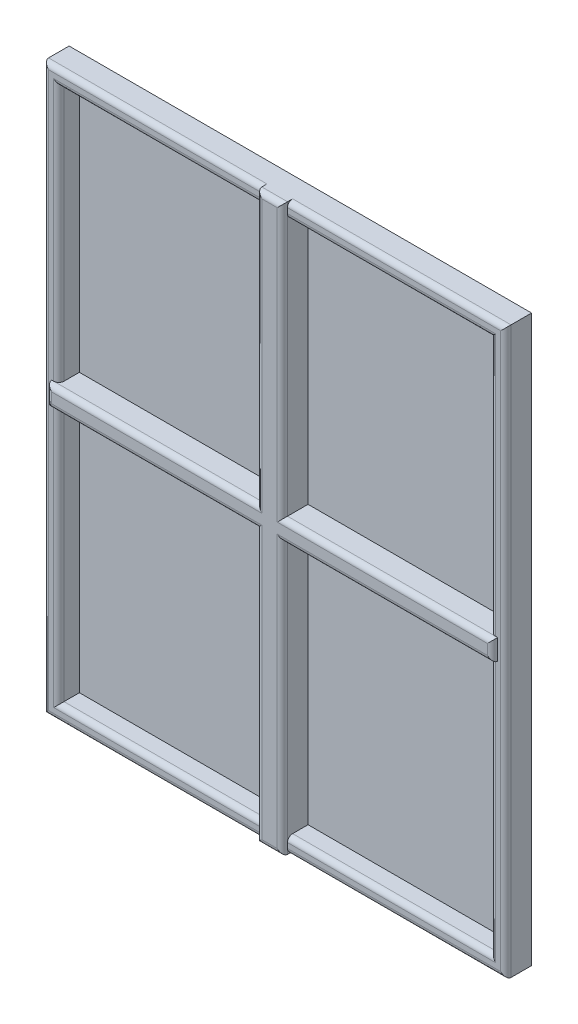
SolidWorks part; units mm, degrees
ref_plane "Front Plane" through (0, 0, 0) normal (0, 0, 1) x (1, 0, 0)
ref_plane "Top Plane" through (0, 0, 0) normal (0, 1, 0) x (1, 0, 0)
ref_plane "Right Plane" through (0, 0, 0) normal (1, 0, 0) x (0, 0, -1)
sketch "Sketch1" plane through (0, 0, 0) normal (0, 0, 1) x (1, 0, 0)
  line L0 (-420, -520) -> (-420, 520)
  line L1 (-450, -550) -> (450, -550)
  line L2 (-450, -550) -> (-450, 550)
  line L3 (-450, 550) -> (450, 550)
  line L4 (450, -550) -> (450, 550)
  line L5 (-450, -550) -> (450, 550) construction
  line L6 (-450, 550) -> (450, -550) construction
  line L7 (-420, 520) -> (420, 520)
  line L8 (420, -520) -> (420, 520)
  line L9 (-420, -520) -> (420, -520)
  point P0 (0, 0)
  dimension "D1" = 1100
  dimension "D2" = 900
  dimension "D3" = 30
extrude "Boss-Extrude1" add sketch "Sketch1" along normal blind 50
fillet "Fillet1" radius 10 8 edges at (420, 0, 50) (0, 520, 50) (-420, 0, 50) (0, -520, 50) (0, -550, 50) (-450, 0, 50) (0, 550, 50) (450, 0, 50)
sketch "Sketch2" plane through (0, 0, 0) normal (0, 0, 1) x (1, 0, 0)
  line L0 (0, 550) -> (0, -550) construction
  line L1 (-450, 550) -> (450, 550) construction
  line L2 (450, -550) -> (-450, -550) construction
  line L3 (-450, 0) -> (450, 0) construction
  line L4 (-450, -550) -> (-450, 550) construction
  line L5 (450, 550) -> (450, -550) construction
  line L6 (-430, -530) -> (-430, 530) construction
  line L7 (-25, 550) -> (25, 550)
  line L8 (-25, 550) -> (-25, -550)
  line L9 (-25, -550) -> (25, -550)
  line L10 (25, 550) -> (25, -550)
  line L11 (-434, 20) -> (434, 20)
  line L12 (-434, 20) -> (-434, -20)
  line L13 (-434, -20) -> (434, -20)
  line L14 (434, 20) -> (434, -20)
  line L15 (430, 530) -> (430, -530) construction
  dimension "D1" = 4
  dimension "D2" = 4
  dimension "D3" = 40
  dimension "D4" = 50
extrude "Boss-Extrude2" add sketch "Sketch2" along normal blind 60 contours L13 L8 L9 L10 | L12 L11 L14 L13 | L10 L9 L8 L7 region at (0, -285, 0)
fillet "Fillet2" radius 10 12 edges at (0, -550, 60) (-25, -285, 60) (-229.5, -20, 60) (-434, 0, 60) (-229.5, 20, 60) (-25, 285, 60) (0, 550, 60) (25, 285, 60) (229.5, 20, 60) (434, 0, 60) (229.5, -20, 60) (25, -285, 60)
sketch "Sketch3" plane through (0, 0, 0) normal (0, 0, 1) x (1, 0, 0)
  line L1 (-430, 530) -> (430, 530)
  line L2 (-430, 530) -> (-430, -530)
  line L3 (-430, -530) -> (430, -530)
  line L4 (430, 530) -> (430, -530)
extrude "Boss-Extrude3" add sketch "Sketch3" along normal blind 10 separate body
scale "Scale2" bodies to scale 102 103 scale about origin uniform scaling yes scale factor 0.25
scale "Scale3" bodies to scale 105 106 scale about origin uniform scaling yes scale factor 0.32
